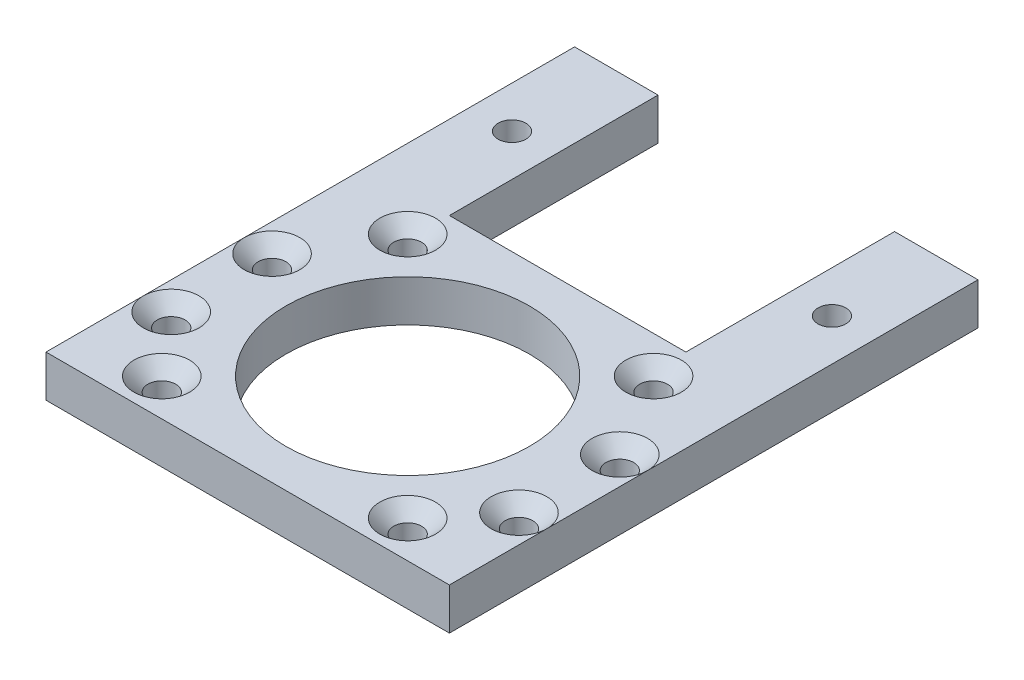
SolidWorks part; units mm, degrees
material "1060 合金"
ref_plane "前视基准面" through (0, 0, 0) normal (0, 0, 1) x (1, 0, 0)
ref_plane "上视基准面" through (0, 0, 0) normal (0, 1, 0) x (1, 0, 0)
ref_plane "右视基准面" through (0, 0, 0) normal (1, 0, 0) x (0, 0, -1)
sketch "草图1" plane through (0, 0, 0) normal (0, 1, 0) x (1, 0, 0)
  line L0 (0, 0) -> (-17.6777, 17.6777) construction
  line L1 (-29, 23) -> (29, 23)
  line L2 (-29, 23) -> (-29, -23)
  line L3 (-29, -23) -> (29, -23)
  line L5 (0, 0) -> (-25, 0) construction
  line L6 (0, 0) -> (-17.6777, -17.6777) construction
  line L7 (29, 23) -> (29, -23)
  line L8 (0, 31.2136) -> (0, -34.3664) construction
  circle A0 centre (0, 0) radius 17.5
  circle A1 centre (0, 0) radius 25 construction
  circle A2 centre (-17.6777, 17.6777) radius 2
  circle A3 centre (-17.6777, -17.6777) radius 2
  circle A4 centre (17.6777, 17.6777) radius 2
  circle A5 centre (17.6777, -17.6777) radius 2
  circle A6 centre (-25, 5.5) radius 2
  circle A7 centre (-25, -9) radius 2
  circle A8 centre (25, -9) radius 2
  circle A9 centre (25, 5.5) radius 2
  point P11 (-29, 0)
  point P23 (0, -23)
  point P24 (0, 23)
  dimension "D1" = 35
  dimension "D2" = 50
  dimension "D5" = 4
  dimension "D8" = 4
  dimension "D3" = 58
  dimension "D4" = 46
  dimension "D6" = 45
  dimension "D7" = 45
  dimension "D10" = 4
  dimension "D11" = 14.5
  dimension "D12" = 14
extrude "凸台-拉伸1" add sketch "草图1" along normal blind 6 contours L1 L2 L3 A3 A2 region at (0, 0, -22.2597)
sketch "草图2" plane through (0, 0, 0) normal (0, 1, 0) x (1, 0, 0)
  line L0 (0, 23) -> (0, -23) construction
  line L1 (-29, 23) -> (-17, 23)
  line L2 (-29, 23) -> (-29, 53)
  line L3 (-29, 53) -> (-17, 53)
  line L4 (-17, 23) -> (-17, 53)
  line L5 (-29, 23) -> (29, 23) construction
  line L6 (-29, -23) -> (29, -23) construction
  line L7 (-29, 0) -> (29, 0) construction
  line L8 (-29, 23) -> (-29, -23) construction
  line L9 (29, 23) -> (29, -23) construction
  line L10 (17, 23) -> (17, 53)
  line L11 (29, 53) -> (17, 53)
  line L12 (29, 23) -> (29, 53)
  line L13 (29, 23) -> (17, 23)
  circle A0 centre (-23, 38) radius 2
  circle A1 centre (23, 38) radius 2
  point P24 (-29, 38)
  point P25 (-23, 53)
  point P28 (23, 53)
  dimension "D3" = 4
  dimension "D1" = 12
  dimension "D2" = 30
extrude "凸台-拉伸2" add sketch "草图2" along normal up to surface (6 mm away) up to face at (25, 6, 11)
chamfer "倒角1" distance 2 angle 45 8 edges at (17.6777, 6, -15.6777) (25, 6, -3.5) (25, 6, 11) (17.6777, 6, 19.6777) (-17.6777, 6, 19.6777) (-25, 6, 11) (-25, 6, -3.5) (-17.6777, 6, -15.6777)
